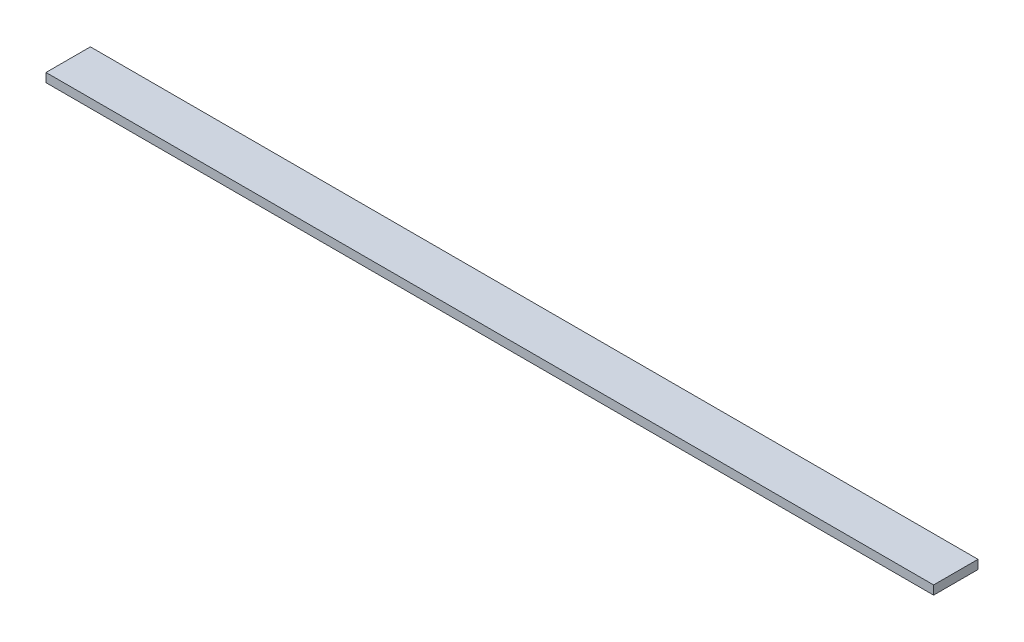
SolidWorks part; units mm, degrees
ref_plane "Front Plane" through (0, 0, 0) normal (0, 0, 1) x (1, 0, 0)
ref_plane "Top Plane" through (0, 0, 0) normal (0, 1, 0) x (1, 0, 0)
ref_plane "Right Plane" through (0, 0, 0) normal (1, 0, 0) x (0, 0, -1)
sketch "Sketch1" plane through (0, 0, 0) normal (0, 1, 0) x (1, 0, 0)
  line L1 (127, -6.35) -> (-127, -6.35)
  line L2 (127, -6.35) -> (127, 6.35)
  line L3 (127, 6.35) -> (-127, 6.35)
  line L4 (-127, -6.35) -> (-127, 6.35)
  line L5 (127, -6.35) -> (-127, 6.35) construction
  line L6 (127, 6.35) -> (-127, -6.35) construction
  point P0 (0, 0)
  dimension "D1" = 254
  dimension "D2" = 12.7
extrude "Boss-Extrude1" add sketch "Sketch1" along normal blind 2.54 contours L3 L4 L1 L2
